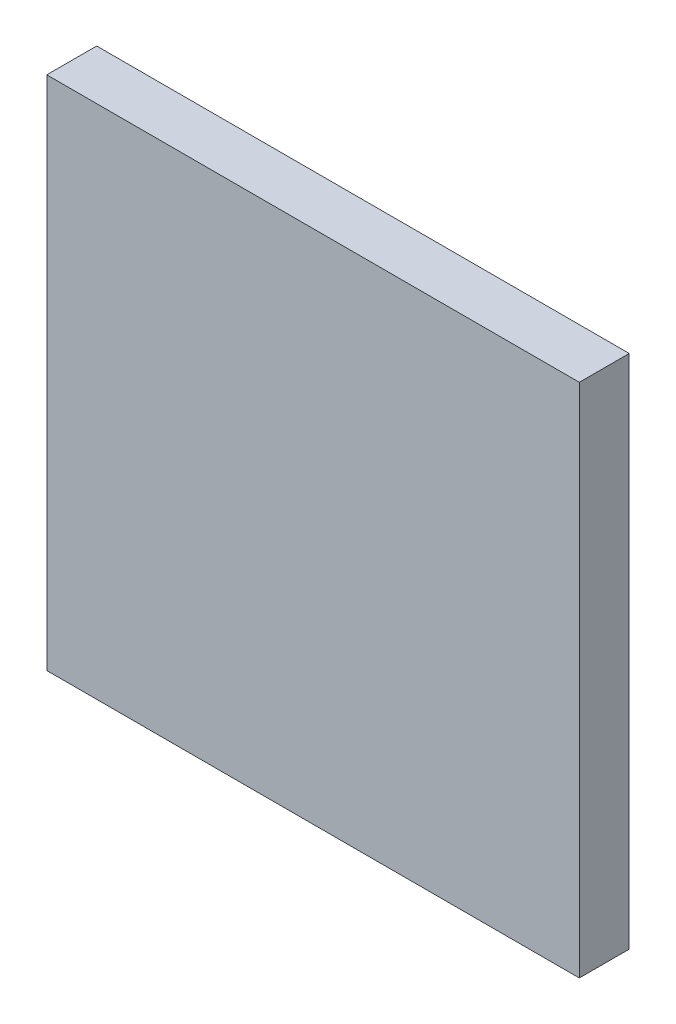
SolidWorks part; units mm, degrees
ref_plane "Ön Düzlem" through (0, 0, 0) normal (0, 0, 1) x (1, 0, 0)
ref_plane "Üst Düzlem" through (0, 0, 0) normal (0, 1, 0) x (1, 0, 0)
ref_plane "Sağ Düzlem" through (0, 0, 0) normal (1, 0, 0) x (0, 0, -1)
sketch "Çizim1" plane through (0, 0, 0) normal (0, 0, 1) x (1, 0, 0)
  line L1 (0, 0) -> (320, 0)
  line L2 (0, 0) -> (0, -310)
  line L3 (0, -310) -> (320, -310)
  line L4 (320, 0) -> (320, -310)
  dimension "D1" = 320
  dimension "D2" = 310
base flange "Taban-Flanş1" sketch "Çizim1" thickness 30 reverse thickness direction no parameters "D1"=20
sketch "Büküm-Çizgileri1" [suppressed] plane through (0, 0, 0) normal (0, 1, 0) x (1, 0, 0)
sketch "Sınırlandırma-Kutusu1" [suppressed] plane through (0, 0, 0) normal (0, 1, 0) x (1, 0, 0)
sheet metal parameters "Sac-Levha1" thickness 30 parameters "D1"=20
flat pattern "Düz-Çoğaltma1" [suppressed]
sketch "Büküm-Çizgileri2" plane through (0, 0, 0) normal (0, 1, 0) x (1, 0, 0)
sketch3d "Sınırlandırma-Kutusu2" [suppressed]
  line L0 (0, -310, 0) -> (-320, -310, 0) construction
  line L1 (0, 0, 0) -> (-320, 0, 0) construction
  line L2 (0, -310, 0) -> (0, 0, 0) construction
  line L3 (-320, -310, 0) -> (-320, 0, 0) construction
